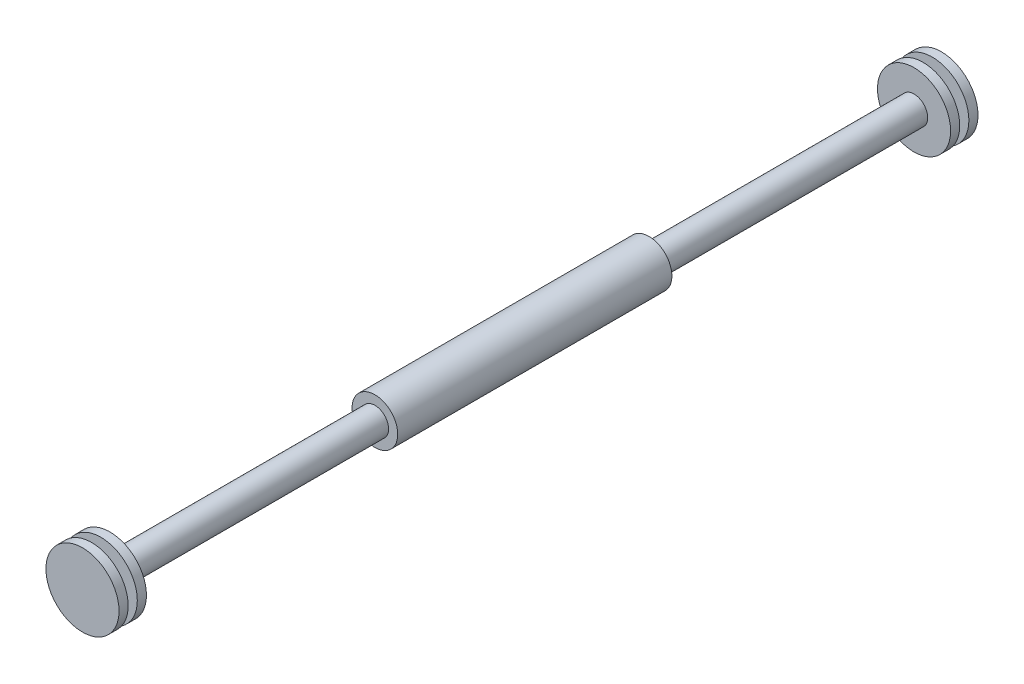
SolidWorks part; units mm, degrees
ref_plane "前视基准面" through (0, 0, 0) normal (0, 0, 1) x (1, 0, 0)
ref_plane "上视基准面" through (0, 0, 0) normal (0, 1, 0) x (1, 0, 0)
ref_plane "右视基准面" through (0, 0, 0) normal (1, 0, 0) x (0, 0, -1)
other "Configuration Table"
sketch "草图1" plane through (0, 0, 0) normal (0, 0, 1) x (1, 0, 0)
  circle A0 centre (0, 0) radius 3
extrude "凸台-拉伸1" add sketch "草图1" along normal blind 180
sketch "草图2" plane through (0, 0, 180) normal (0, 0, 1) x (1, 0, 0)
  circle A2 centre (0, 0) radius 8
  circle A3 centre (0, 0) radius 8
  dimension "D1" = 5
extrude "凸台-拉伸2" add sketch "草图2" against normal blind 2
extrude "凸台-拉伸3" add sketch "草图2<2>" along normal blind 2 from surface starting at face at (3, 0, 0)
sketch "草图2<2>" plane through (0, 0, 180) normal (0, 0, 1) x (1, 0, 0) same geometry as "草图2"
extrude "凸台-拉伸4" add sketch "草图1<2>" against normal blind 2
sketch "草图1<2>" plane through (0, 0, 0) normal (0, 0, 1) x (1, 0, 0) same geometry as "草图1"
extrude "凸台-拉伸5" add sketch "草图1<3>" along normal blind 2 from surface starting at face at (8, 0, 180)
sketch "草图1<3>" plane through (0, 0, 0) normal (0, 0, 1) x (1, 0, 0) same geometry as "草图1"
extrude "凸台-拉伸6" add sketch "草图2<3>" along normal blind 2 from surface starting at face at (3, 0, 182)
sketch "草图2<3>" plane through (0, 0, 180) normal (0, 0, 1) x (1, 0, 0) same geometry as "草图2"
extrude "凸台-拉伸7" add sketch "草图2<4>" against normal blind 2 from surface starting at face at (3, 0, -2)
sketch "草图2<4>" plane through (0, 0, 180) normal (0, 0, 1) x (1, 0, 0) same geometry as "草图2"
sketch "草图3" plane through (0, 0, 184) normal (0, 0, 1) x (1, 0, 0)
  circle A0 centre (0, 0) radius 5
extrude "凸台-拉伸10" add sketch "草图3" against normal blind 60 from offset 64 offset against normal yes
